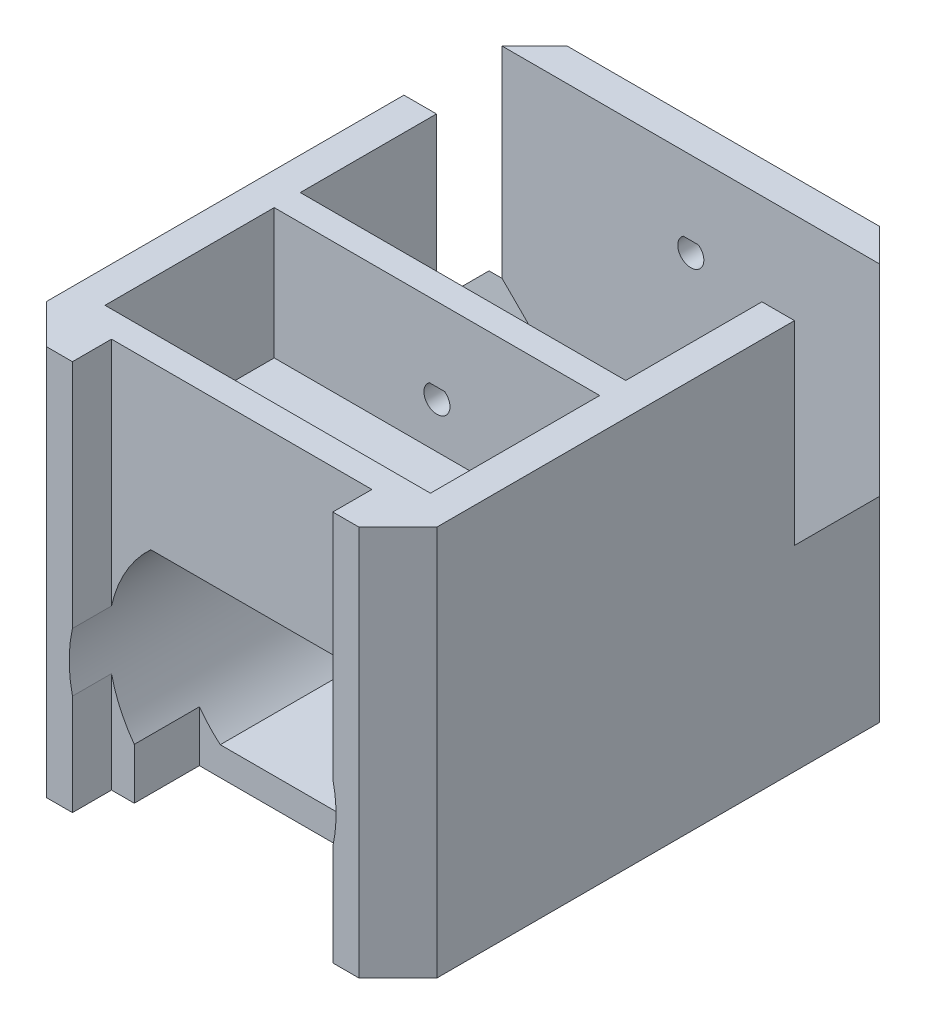
SolidWorks part; units mm, degrees
ref_plane "Front Plane" through (0, 0, 0) normal (0, 0, 1) x (1, 0, 0)
ref_plane "Top Plane" through (0, 0, 0) normal (0, 1, 0) x (1, 0, 0)
ref_plane "Right Plane" through (0, 0, 0) normal (1, 0, 0) x (0, 0, -1)
sketch "Sketch1" plane through (0, 0, 0) normal (0, 0, 1) x (1, 0, 0)
  line L1 (-15, -20) -> (15, -20)
  line L2 (-15, -20) -> (-15, 20)
  line L3 (-15, 20) -> (15, 20)
  line L4 (15, -20) -> (15, 20)
  line L5 (-15, -20) -> (15, 20) construction
  line L6 (-15, 20) -> (15, -20) construction
  point P0 (0, 0)
  dimension "D1" = 30
  dimension "D2" = 40
extrude "Boss-Extrude1" add sketch "Sketch1" along normal blind 40
sketch "Sketch2" plane through (0, 0, 40) normal (0, 0, 1) x (1, 0, 0)
  line L5 (-6.9866, -2.5) -> (6.9866, -2.5)
  line L7 (-6.6464, -17.803) -> (6.6464, -17.803)
  arc A4 (-6.9866, -2.5) -> (-6.6464, -17.803) centre (0, -10) ccw
  arc A5 (6.6464, -17.803) -> (6.9866, -2.5) centre (0, -10) ccw
  point P0 (0, -10)
  dimension "D2" = 20.5
extrude "Cut-Extrude1" cut sketch "Sketch2" against normal blind 35
sketch "Sketch4" plane through (0, 20, 0) normal (0, 1, 0) x (1, 0, 0)
  line L1 (-12.5, -37.5) -> (12.5, -37.5)
  line L2 (-12.5, -37.5) -> (-12.5, -2.5)
  line L3 (-12.5, -2.5) -> (12.5, -2.5)
  line L4 (12.5, -37.5) -> (12.5, -2.5)
  point P0 (0, -20)
  dimension "D1" = 25
  dimension "D2" = 35
extrude "Cut-Extrude3" cut sketch "Sketch4" against normal blind 20
sketch "Sketch5" plane through (0, 0, 0) normal (0, 1, 0) x (1, 0, 0)
  line L0 (12.5, -37.5) -> (12.5, -2.5) construction
  line L1 (-12.5, -2.5) -> (12.5, -2.5)
  line L2 (-12.5, -2.5) -> (-12.5, -20)
  line L3 (-12.5, -20) -> (12.5, -20)
  line L4 (12.5, -2.5) -> (12.5, -20)
extrude "Cut-Extrude4" cut sketch "Sketch5" against normal blind 20
sketch "Sketch13" plane through (0, 0, 0) normal (0, 1, 0) x (1, 0, 0)
  line L0 (12.5, -37.5) -> (12.5, -20) construction
  line L1 (-12.5, -20) -> (12.5, -20)
  line L2 (-12.5, -20) -> (-12.5, -22.0007)
  line L3 (-12.5, -22.0007) -> (12.5, -22.0007)
  line L4 (12.5, -20) -> (12.5, -22.0007)
extrude "Boss-Extrude3" add sketch "Sketch13" along normal up to surface (20 mm away) up to face at (0, 20, 20)
sketch "Sketch8" plane through (0, 0, 40) normal (0, 0, 1) x (1, 0, 0)
  line L0 (-0.5467, -9.1627) -> (0.5467, -9.1627)
  arc A3 (-0.5467, -9.1627) -> (0.5467, -9.1627) centre (0, -10.2278) ccw
extrude "Cut-Extrude5" cut sketch "Sketch8" against normal up to surface (40 mm away) up to face at (0, 0, 0)
sketch "Sketch9" plane through (0, 0, 0) normal (0, 0, -1) x (-1, 0, 0)
  line L1 (-0.5842, 4.3116) -> (0.5842, 4.3116)
  arc A0 (-0.5842, 4.3116) -> (0.5842, 4.3116) centre (0, 3.5) ccw
  dimension "D2" = 2
extrude "Cut-Extrude6" cut sketch "Sketch9" against normal up to surface (40 mm away) up to face at (0, -10.1897, 40)
sketch "Sketch10" plane through (0, 0, 40) normal (0, 0, 1) x (1, 0, 0)
  line L0 (15, -20) -> (15, 20) construction
  line L1 (-15, 20) -> (15, 20)
  line L2 (-15, 20) -> (-15, 10)
  line L3 (-15, 10) -> (15, 10)
  line L4 (15, 20) -> (15, 10)
  dimension "D1" = 10
extrude "Cut-Extrude9" cut sketch "Sketch10" against normal up to surface (40 mm away) up to face at (0, 3.4058, 0)
chamfer "Chamfer2" distance 3 angle 45 4 edges at (15, -5, 0) (15, -5, 40) (-15, -5, 40) (-15, -5, 0)
sketch "Sketch16" plane through (-12.5, 0, 0) normal (1, 0, 0) x (0, 0, -1)
  line L1 (-2.5, 10) -> (-9.5368, 10)
  line L2 (-2.5, 10) -> (-2.5, -4.4568)
  line L4 (-9.5368, 10) -> (-9.5368, -4.4568)
  line L5 (-9.5368, -4.4568) -> (-2.5, -4.4568)
extrude "Cut-Extrude10" cut sketch "Sketch16" against normal mid plane 57
chamfer "Chamfer3" distance 3 angle 45 2 edges at (12.5, -4.4568, 6.0184) (-12.5, -4.4568, 6.0184)
sketch "Sketch17" plane through (0, 10, 0) normal (0, 1, 0) x (1, 0, 0)
  line L0 (12.5, -37.5) -> (12.5, -22.0007) construction
  line L1 (-12.5, -37.5) -> (12.5, -37.5)
  line L2 (-12.5, -37.5) -> (-12.5, -35)
  line L3 (-12.5, -35) -> (12.5, -35)
  line L4 (12.5, -37.5) -> (12.5, -35)
  dimension "D1" = 2.5
extrude "Boss-Extrude4" add sketch "Sketch17" against normal up to surface (10 mm away) up to face at (0, 0, 29.7504)
sketch "Sketch18" plane through (0, 10, 0) normal (0, 1, 0) x (1, 0, 0)
  line L0 (-10, -40) -> (10, -40)
  line L1 (-12, -40) -> (12, -40) construction
  line L5 (-10, -40) -> (10, -40)
  line L6 (-10, -40) -> (-10, -37)
  line L7 (-10, -37) -> (10, -37)
  line L8 (10, -40) -> (10, -37)
  point P5 (0, -40)
  line M15 (-12, -40) -> (12, -40)
  dimension "D1" = 20
  dimension "D2" = 3
extrude "Cut-Extrude13" cut sketch "Sketch18" against normal up to surface (30 mm away) contours L8 L7 L6 M15 region at (0, 10, 38.5) up to face at (0, -20, 11.25)
sketch "Sketch19" plane through (0, -20, 0) normal (0, -1, 0) x (1, 0, 0)
  line L0 (-8.25, 37) -> (8.25, 37)
  line L1 (10, 37) -> (-10, 37) construction
  line L5 (-8.25, 37) -> (8.25, 37)
  line L6 (-8.25, 37) -> (-8.25, 32)
  line L7 (-8.25, 32) -> (8.25, 32)
  line L8 (8.25, 37) -> (8.25, 32)
  point P5 (0, 37)
  line M18 (10, 37) -> (-10, 37)
  dimension "D1" = 16.5
  dimension "D2" = 5
extrude "Cut-Extrude14" cut sketch "Sketch19" against normal blind 10 contours L8 L6 L7 M18 region at (0, -20, 34.5)
sketch "Sketch20" plane through (0, 0, 20) normal (0, 0, -1) x (-1, 0, 0)
  line L0 (10.25, -10) -> (12.5, -10)
  line L1 (-12.5, -10) -> (-10.25, -10)
  line L2 (-12.5, -10) -> (-12.5, -20)
  line L3 (-12.5, -20) -> (12.5, -20)
  line L4 (12.5, -20) -> (12.5, 10)
  line L5 (12.5, 10) -> (-12.5, 10)
  line L6 (-12.5, 10) -> (-12.5, -20)
  line L7 (-12.5, -20) -> (12.5, -20)
  line L8 (12.5, -20) -> (12.5, -10)
  line L10 (-12.5, -10) -> (-12.5, -20)
  line L11 (-12.5, -20) -> (12.5, -20)
  line L12 (12.5, -10) -> (12.5, -20)
  line L13 (-6.6464, -17.803) -> (6.6464, -17.803)
  arc A0 (6.6464, -17.803) -> (6.9866, -2.5) centre (0, -10) ccw construction
  arc A1 (6.6464, -17.803) -> (10.25, -10) centre (0, -10) ccw
  arc A2 (-6.9866, -2.5) -> (-6.6464, -17.803) centre (0, -10) ccw construction
  arc A3 (-10.25, -10) -> (-6.6464, -17.803) centre (0, -10) ccw
  line M7 (12.5, -20) -> (12.5, 10)
  line M9 (-12.5, 10) -> (-12.5, -20)
  line M10 (-12.5, -20) -> (12.5, -20)
  line M11 (6.6464, -17.803) -> (-6.6464, -17.803)
  arc M12 (-6.6464, -17.803) -> (-6.9866, -2.5) centre (0, -10) cw
  arc M14 (6.9866, -2.5) -> (6.6464, -17.803) centre (0, -10) cw
  dimension "D1" = 0
extrude "Boss-Extrude5" add sketch "Sketch20" along normal blind 7.5 contours L1 L0 M9 M10 M7 M14 M11 M12 region at (-11.375, -10.2693, 20)
sketch "Sketch22" plane through (0, 0, 12.5) normal (0, 0, -1) x (-1, 0, 0)
  line L0 (12.5, -20) -> (12.5, -10) construction
  line L1 (-12.5, -20) -> (12.5, -20)
  line L2 (-12.5, -20) -> (-12.5, -15)
  line L3 (-12.5, -15) -> (12.5, -15)
  line L4 (12.5, -20) -> (12.5, -15)
extrude "Boss-Extrude6" add sketch "Sketch22" along normal blind 1
